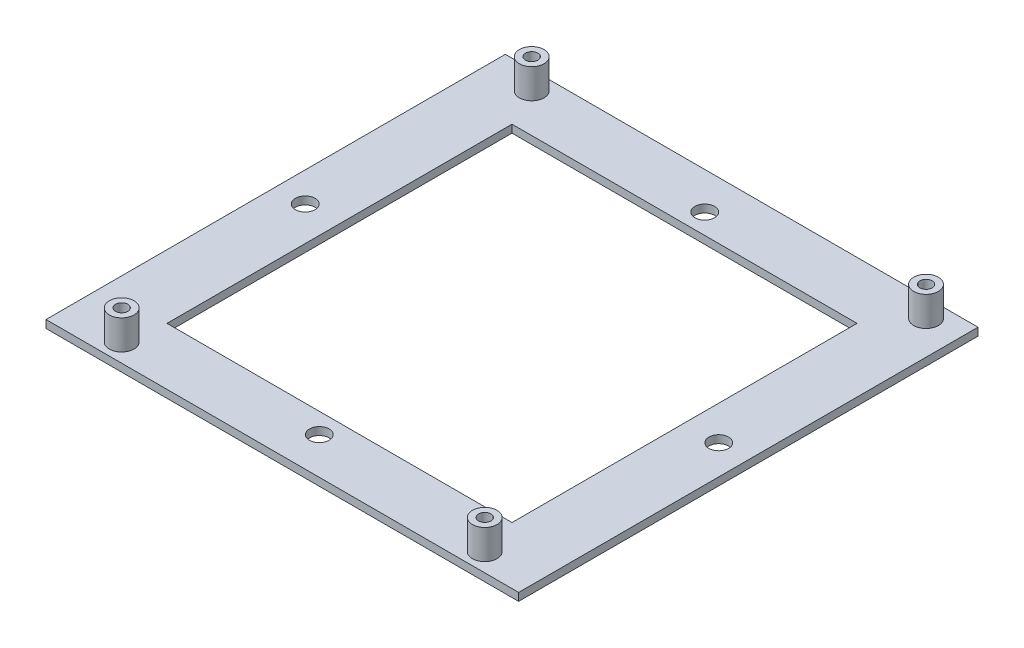
SolidWorks part; units mm, degrees
ref_plane "Front Plane" through (0, 0, 0) normal (0, 0, 1) x (1, 0, 0)
ref_plane "Top Plane" through (0, 0, 0) normal (0, 1, 0) x (1, 0, 0)
ref_plane "Right Plane" through (0, 0, 0) normal (1, 0, 0) x (0, 0, -1)
sketch "Sketch1" plane through (0, 0, 0) normal (0, 1, 0) x (1, 0, 0)
  line L1 (-47.95, -46.6) -> (47.95, -46.6)
  line L2 (-47.95, -46.6) -> (-47.95, 46.6)
  line L3 (-47.95, 46.6) -> (47.95, 46.6)
  line L4 (47.95, -46.6) -> (47.95, 46.6)
  line L5 (-47.95, -46.6) -> (47.95, 46.6) construction
  line L6 (-47.95, 46.6) -> (47.95, -46.6) construction
  line L7 (-35, -35) -> (35, -35)
  line L8 (-35, -35) -> (-35, 35)
  line L9 (-35, 35) -> (35, 35)
  line L10 (35, -35) -> (35, 35)
  line L11 (-35, -35) -> (35, 35) construction
  line L12 (-35, 35) -> (35, -35) construction
  circle A0 centre (0, 39.1) radius 2
  circle A1 centre (41.95, 0) radius 2
  circle A2 centre (0, -39.1) radius 2
  circle A3 centre (-41.95, 0) radius 2
  point P0 (0, 0)
  point P6 (0, 0)
  point P11 (0, 39.1)
  point P12 (0, -39.1)
  point P13 (41.95, 0)
  point P14 (-41.95, 0)
extrude "Boss-Extrude1" add sketch "Sketch1" along normal blind 1.58
sketch "Sketch2" plane through (0, 1.58, 0) normal (0, 1, 0) x (1, 0, 0)
  line L0 (41.145, 42.8635) -> (-38.865, 42.8635) construction
  line L1 (-38.865, -957.1365) -> (-38.865, 49042.8635) construction
  line L2 (41.145, -957.1365) -> (41.145, 49042.8635) construction
  line L3 (41.145, 42.8635) -> (41.145, -42.8665) construction
  line L4 (41.145, -42.8665) -> (37.335, -42.8665) construction
  line L5 (37.335, -42.8665) -> (-36.325, -42.8665) construction
  line L6 (-36.325, -42.8665) -> (-38.865, -42.8665) construction
  circle A0 centre (41.145, 42.8635) radius 2.5
  circle A1 centre (-38.865, 42.8635) radius 2.5
  circle A2 centre (-36.325, -42.8665) radius 2.5
  circle A3 centre (37.335, -42.8665) radius 2.5
  point P0 (41.145, 42.8635)
extrude "Boss-Extrude2" add sketch "Sketch2" along normal blind 6
hole_wizard "M3x0.5 Tapped Hole2" positions "3DSketch2" profile "Sketch4" tap size "M3x0.5" standard "ANSI Metric"
sketch3d "3DSketch2"
  line L0 (-38.865, 7.58, -42.8635) -> (-38.865, 1.58, -42.8635) construction
  line L1 (-36.325, 7.58, 42.8665) -> (-36.325, 1.58, 42.8665) construction
  line L2 (37.335, 7.58, 42.8665) -> (37.335, 1.58, 42.8665) construction
  line L3 (41.145, 7.58, -42.8635) -> (41.145, 1.58, -42.8635) construction
  point P0 (-38.865, 7.58, -42.8635)
  point P4 (-36.325, 7.58, 42.8665)
  point P8 (37.335, 7.58, 42.8665)
  point P12 (41.145, 7.58, -42.8635)
sketch "Sketch4" plane through (-38.865, 7.58, -42.8635) normal (1, 0, 0) x (0, 0, 1)
  line L0 (0, 0) -> (0, 6.7511)
  line L1 (0, 6.7511) -> (1.25, 6)
  line L2 (1.25, 6) -> (1.25, 0)
  line L5 (1.25, 0) -> (0, 0)
  line L10 (0, 6.7511) -> (-1.25, 6) construction
  line L11 (0, -6.35) -> (0, 107.95) construction
  dimension "Tap Drill Dia." = 2.5
  dimension "Tap Drill Depth" = 6
  dimension "Drill Angle" = 118
cosmetic thread "Hole Thread5" parameters "D1"=6, "D2"=3
cosmetic thread "Hole Thread6" parameters "D1"=6, "D2"=3
cosmetic thread "Hole Thread7" parameters "D1"=6, "D2"=3
cosmetic thread "Hole Thread8" parameters "D1"=6, "D2"=3
